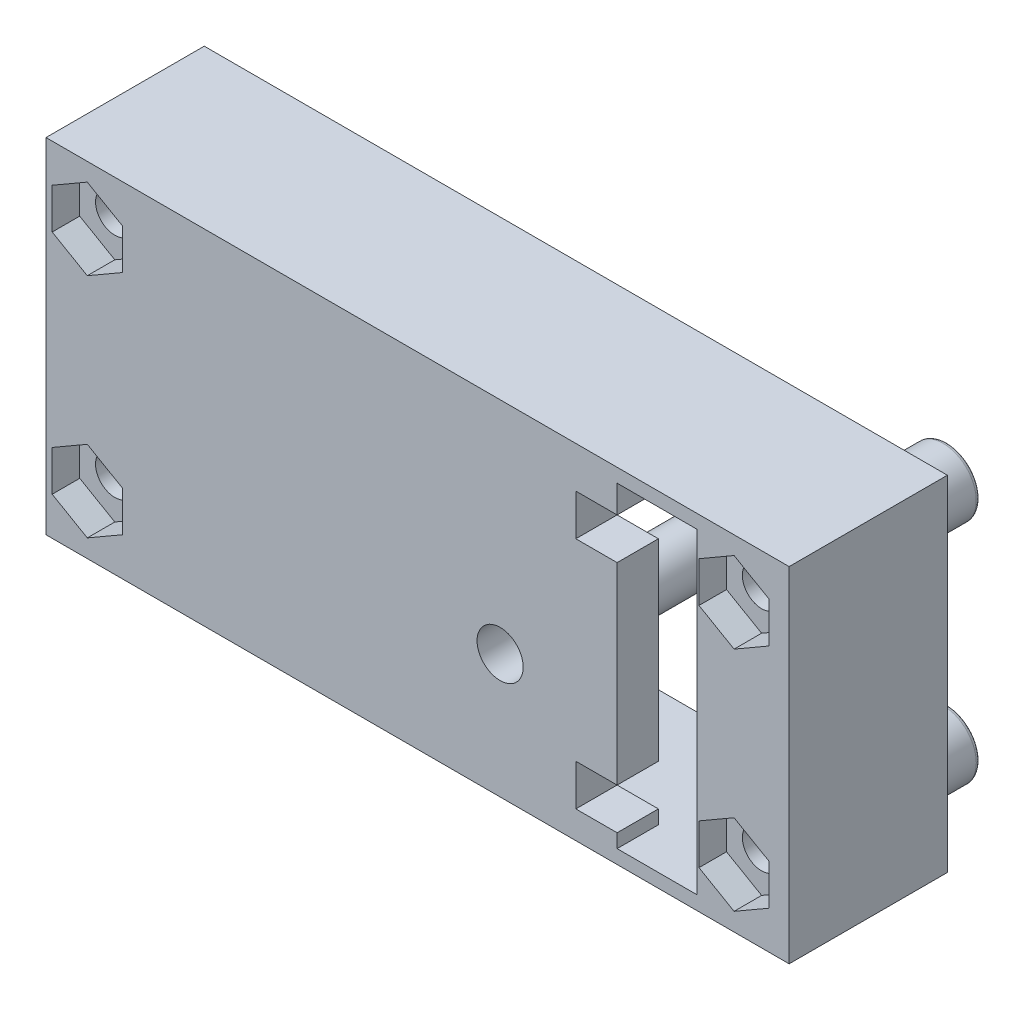
SolidWorks part; units mm, degrees
ref_plane "Front Plane" through (0, 0, 0) normal (0, 0, 1) x (1, 0, 0)
ref_plane "Top Plane" through (0, 0, 0) normal (0, 1, 0) x (1, 0, 0)
ref_plane "Right Plane" through (0, 0, 0) normal (1, 0, 0) x (0, 0, -1)
sketch "Sketch1" plane through (0, 0, 0) normal (0, 0, 1) x (1, 0, 0)
  line L1 (27, -12.5) -> (-27, -12.5)
  line L2 (27, -12.5) -> (27, 12.5)
  line L3 (27, 12.5) -> (-27, 12.5)
  line L4 (-27, -12.5) -> (-27, 12.5)
  line L5 (27, -12.5) -> (-27, 12.5) construction
  line L6 (27, 12.5) -> (-27, -12.5) construction
  line L7 (26, -11.5) -> (-26, -11.5)
  line L8 (26, -11.5) -> (26, 11.5)
  line L9 (26, 11.5) -> (-26, 11.5)
  line L10 (-26, -11.5) -> (-26, 11.5)
  line L11 (26, -11.5) -> (-26, 11.5) construction
  line L12 (26, 11.5) -> (-26, -11.5) construction
  point P0 (0, 0)
  point P6 (0, 0)
  dimension "D1" = 52
  dimension "D2" = 23
  dimension "D3" = 1
  dimension "D4" = 1
extrude "Boss-Extrude1" add sketch "Sketch1" along normal blind 8.5
sketch "Sketch2" plane through (0, 0, 8.5) normal (0, 0, 1) x (1, 0, 0)
  line L1 (27, -12.5) -> (-27, -12.5)
  line L2 (27, -12.5) -> (27, 12.5)
  line L3 (27, 12.5) -> (-27, 12.5)
  line L4 (-27, -12.5) -> (-27, 12.5)
  line L5 (27, -12.5) -> (-27, 12.5) construction
  line L6 (27, 12.5) -> (-27, -12.5) construction
  point P0 (0, 0)
extrude "Boss-Extrude2" add sketch "Sketch2" along normal blind 3
sketch "Sketch4" plane through (0, 0, 8.5) normal (0, 0, -1) x (-1, 0, 0)
  line L0 (26, -11.5) -> (-26, -11.5) construction
  line L1 (-20.3, 11.5) -> (-14.5, 11.5)
  line L2 (-20.3, 11.5) -> (-20.3, -11.5)
  line L3 (-20.3, -11.5) -> (-14.5, -11.5)
  line L4 (-14.5, 11.5) -> (-14.5, -11.5)
  line L5 (26, 11.5) -> (26, -11.5) construction
  line L6 (-26, 11.5) -> (26, 11.5) construction
  dimension "D1" = 5.8
  dimension "D2" = 40.5
extrude "Cut-Extrude1" cut sketch "Sketch4" against normal blind 3
sketch "Sketch5" plane through (0, 0, 8.5) normal (0, 0, -1) x (-1, 0, 0)
  circle A0 centre (-10, 0) radius 2
  dimension "D1" = 4
  dimension "D2" = 10
extrude "Boss-Extrude3" add sketch "Sketch5" along normal blind 9.7
fillet "Fillet1" radius 2 1 edges at (12, 0, 8.5)
sketch "Sketch6" plane through (0, 0, 8.5) normal (0, 0, -1) x (-1, 0, 0)
  line L0 (24, 8.25) -> (24, -8.25) construction
  line L1 (26, 11.5) -> (26, -11.5) construction
  line L2 (-23, 8.25) -> (-23, -8.25) construction
  line L3 (-26, -11.5) -> (-26, 11.5) construction
  line L4 (-27, -12.5) -> (-27, 12.5) construction
  circle A0 centre (24, 8.25) radius 1.4
  circle A1 centre (24, -8.25) radius 1.4
  circle A2 centre (-23, 8.25) radius 1.4
  circle A3 centre (-23, -8.25) radius 1.4
  point P4 (24, 0)
  point P6 (0, 0)
  point P17 (-23, 0)
  dimension "D2" = 2.8
  dimension "D3" = 2.8
  dimension "D4" = 2
  dimension "D5" = 16.5
  dimension "D6" = 4
  dimension "D1" = 16.5
extrude "Cut-Extrude2" cut sketch "Sketch6" against normal blind 10
sketch "Sketch8" plane through (0, 0, 11.5) normal (0, 0, 1) x (1, 0, 0)
  line L1 (-26.55, 9.7222) -> (-26.55, 6.7778)
  line L2 (-26.55, 6.7778) -> (-24, 5.3055)
  line L3 (-24, 5.3055) -> (-21.45, 6.7778)
  line L4 (-21.45, 6.7778) -> (-21.45, 9.7222)
  line L5 (-21.45, 9.7222) -> (-24, 11.1945)
  line L6 (-24, 11.1945) -> (-26.55, 9.7222)
  line L7 (-24, -5.3055) -> (-26.55, -6.7778)
  line L8 (-26.55, -6.7778) -> (-26.55, -9.7222)
  line L9 (-26.55, -9.7222) -> (-24, -11.1945)
  line L10 (-24, -11.1945) -> (-21.45, -9.7222)
  line L11 (-21.45, -9.7222) -> (-21.45, -6.7778)
  line L12 (-21.45, -6.7778) -> (-24, -5.3055)
  line L13 (23, 11.1945) -> (20.45, 9.7222)
  line L14 (-27, 12.5) -> (-27, -12.5) construction
  line L15 (20.45, 9.7222) -> (20.45, 6.7778)
  line L16 (20.45, 6.7778) -> (23, 5.3055)
  line L17 (23, 5.3055) -> (25.55, 6.7778)
  line L18 (25.55, 6.7778) -> (25.55, 9.7222)
  line L19 (25.55, 9.7222) -> (23, 11.1945)
  line L20 (23, -5.3055) -> (20.45, -6.7778)
  line L21 (20.45, -6.7778) -> (20.45, -9.7222)
  line L22 (20.45, -9.7222) -> (23, -11.1945)
  line L23 (23, -11.1945) -> (25.55, -9.7222)
  line L24 (25.55, -9.7222) -> (25.55, -6.7778)
  line L25 (25.55, -6.7778) -> (23, -5.3055)
  circle A0 centre (-24, 8.25) radius 2.55 construction
  circle A1 centre (-24, -8.25) radius 2.55 construction
  circle A2 centre (23, 8.25) radius 2.55 construction
  circle A3 centre (23, -8.25) radius 2.55 construction
  dimension "D2" = 5.1
extrude "Cut-Extrude3" cut sketch "Sketch8" against normal blind 2
sketch "Sketch10" plane through (0, 0, 8.5) normal (0, 0, -1) x (-1, 0, 0)
  line L1 (26, 11.5) -> (17.3098, 11.5)
  line L2 (26, 11.5) -> (26, 3.9581)
  line L3 (26, 3.9581) -> (17.3098, 3.9581)
  line L4 (17.3098, 11.5) -> (17.3098, 3.9581)
  line L5 (26, -11.5) -> (16.8129, -11.5)
  line L6 (26, -11.5) -> (26, -4.0462)
  line L7 (26, -4.0462) -> (16.8129, -4.0462)
  line L8 (16.8129, -11.5) -> (16.8129, -4.0462)
  line L9 (-26, 11.5) -> (-20.6838, 11.5)
  line L10 (-26, 11.5) -> (-26, 4.9094)
  line L11 (-26, 4.9094) -> (-20.6838, 4.9094)
  line L12 (-20.6838, 11.5) -> (-20.6838, 4.9094)
  line L13 (-26, -11.5) -> (-20.0802, -11.5)
  line L14 (-26, -11.5) -> (-26, -4.507)
  line L15 (-26, -4.507) -> (-20.0802, -4.507)
  line L16 (-20.0802, -11.5) -> (-20.0802, -4.507)
  circle A0 centre (24, 8.25) radius 1.4
  circle A1 centre (24, -8.25) radius 1.4
  circle A2 centre (24, -8.25) radius 2.4
  circle A3 centre (24, 8.25) radius 2.4
  circle A4 centre (24, 8.25) radius 1.4 construction
  circle A5 centre (-23, 8.25) radius 1.4
  circle A6 centre (-23, 8.25) radius 2.4
  circle A7 centre (-23, -8.25) radius 1.4
  circle A8 centre (-23, -8.25) radius 2.4
  circle M13 centre (24, 8.25) radius 1.4
  circle M14 centre (24, -8.25) radius 1.4
  dimension "D1" = 1
  dimension "D2" = 1
sketch "Sketch11" plane through (0, 0, 8.5) normal (0, 0, -1) x (-1, 0, 0)
  line L0 (-14.5, -11.5) -> (-14.5, 11.5) construction
  line L1 (-14.5, 9.5) -> (-11.5, 9.5)
  line L2 (-14.5, 9.5) -> (-14.5, 6.5)
  line L3 (-14.5, 6.5) -> (-11.5, 6.5)
  line L4 (-11.5, 9.5) -> (-11.5, 6.5)
  line L5 (-26, 11.5) -> (26, 11.5) construction
  line L6 (-14.5, -7.5) -> (-11.5, -7.5)
  line L7 (-14.5, -7.5) -> (-14.5, -10.5)
  line L8 (-14.5, -10.5) -> (-11.5, -10.5)
  line L9 (-11.5, -7.5) -> (-11.5, -10.5)
  line L10 (26, -11.5) -> (-14.5, -11.5) construction
  line L13 (27, -12.5) -> (-27, -12.5) construction
  circle A0 centre (-6, -3.5) radius 1.675
  dimension "D1" = 3.35
  dimension "D6" = 9
  dimension "D7" = 8.5
  dimension "D2" = 3
  dimension "D3" = 3
  dimension "D4" = 2
  dimension "D5" = 1
extrude "Cut-Extrude4" cut sketch "Sketch11" against normal blind 10
extrude "Boss-Extrude5" add sketch "Sketch10" along normal blind 10 contours L2 A3 M13 | L6 A2 M14 region at (-25.9349, 8.25, 8.5) region at (-21.6651, -8.25, 8.5)
extrude "Boss-Extrude6" add sketch "Sketch10<5>" along normal blind 12.5 contours L10 A6 A5 | L14 A8 A7 region at (20.7511, 8.25, 8.5) region at (25.3321, -8.25, 8.5)
sketch "Sketch10<5>" plane through (0, 0, 8.5) normal (0, 0, -1) x (-1, 0, 0) same geometry as "Sketch10"
sketch "Sketch14" plane through (0, 0, 8.5) normal (0, 0, -1) x (-1, 0, 0)
  line L0 (-14.5, -7.5) -> (-14.5, 6.5) construction
  line L1 (-6, -0.2668) -> (-8.8, -1.8834)
  line L2 (-8.8, -1.8834) -> (-8.8, -5.1166)
  line L3 (-8.8, -5.1166) -> (-6, -6.7332)
  line L4 (-6, -6.7332) -> (-3.2, -5.1166)
  line L5 (-3.2, -5.1166) -> (-3.2, -1.8834)
  line L6 (-3.2, -1.8834) -> (-6, -0.2668)
  line L7 (-6, 0.8879) -> (-9.8, -1.3061)
  line L8 (-9.8, -1.3061) -> (-9.8, -5.6939)
  line L9 (-9.8, -5.6939) -> (-6, -7.8879)
  line L10 (-6, -7.8879) -> (-2.2, -5.6939)
  line L11 (-2.2, -5.6939) -> (-2.2, -1.3061)
  line L12 (-2.2, -1.3061) -> (-6, 0.8879)
  circle A0 centre (-6, -3.5) radius 2.8 construction
  circle A1 centre (-6, -3.5) radius 3.8 construction
  dimension "D1" = 5.6
  dimension "D2" = 1
extrude "Boss-Extrude8" add sketch "Sketch14" along normal blind 2.5
fillet "Fillet3" radius 0.3 12 edges at (8, 0, -1.2) (-21.6, -8.25, -1.5) (-26, -8.25, -1.5) (-25.4, -8.25, -1.5) (-21.6, 8.25, -1.5) (-26, 8.25, -1.5) (-25.4, 8.25, -1.5) (25.4, 8.25, -4) (21.6, 8.25, -4) (20.6, -8.25, -4) (21.6, -8.25, -4) (20.6838, 8.25, -4)
sketch "Sketch15" plane through (0, 0, 6) normal (0, 0, -1) x (-1, 0, 0)
  line L1 (-6, -0.2668) -> (-8.8, -1.8834)
  line L2 (-8.8, -1.8834) -> (-8.8, -5.1166)
  line L3 (-8.8, -5.1166) -> (-6, -6.7332)
  line L4 (-6, -6.7332) -> (-3.2, -5.1166)
  line L5 (-3.2, -5.1166) -> (-3.2, -1.8834)
  line L6 (-3.2, -1.8834) -> (-6, -0.2668)
  circle A0 centre (-6, -3.5) radius 2.8 construction
extrude "Cut-Extrude5" cut sketch "Sketch15" against normal up to surface (2.5 mm away) up to face at (5.9672, -3.3829, 8.5)
chamfer "Chamfer1" distance 1 angle 45 4 edges at (-21.6, -8.25, 8.5) (-21.6, 8.25, 8.5) (25.4, -8.25, 8.5) (25.4, 8.25, 8.5)
